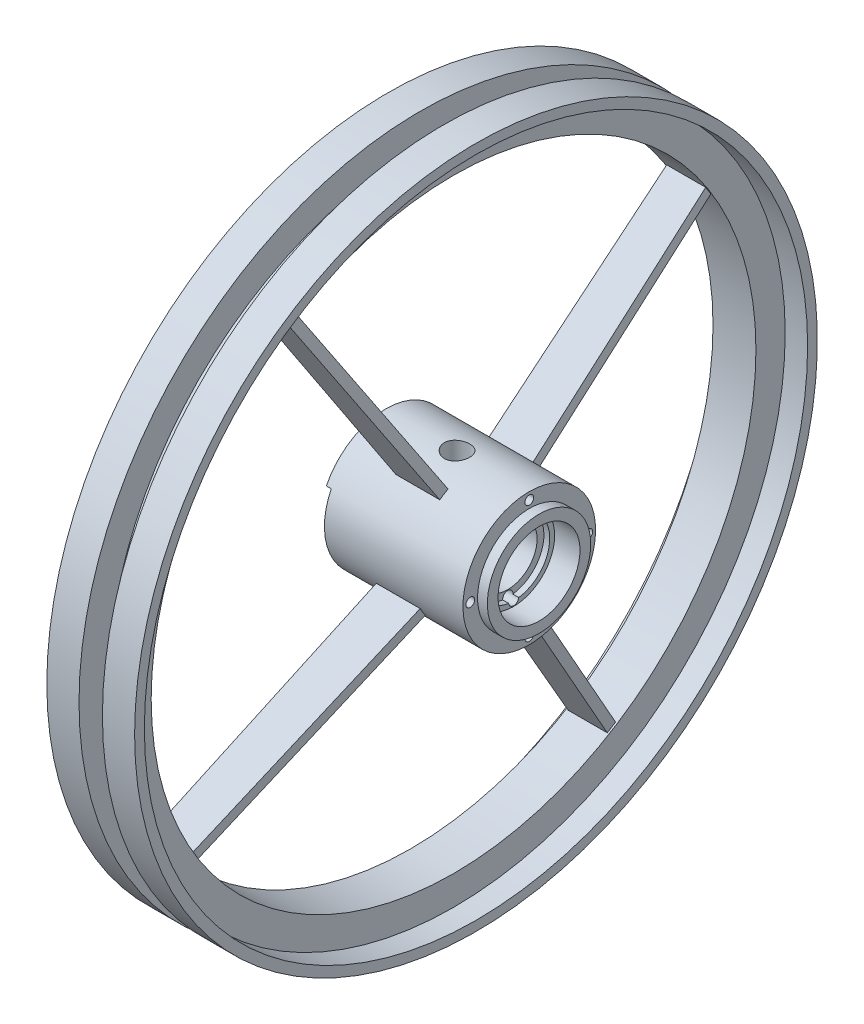
SolidWorks part; units mm, degrees
ref_plane "Front Plane" through (0, 0, 0) normal (0, 0, 1) x (1, 0, 0)
ref_plane "Top Plane" through (0, 0, 0) normal (0, 1, 0) x (1, 0, 0)
ref_plane "Right Plane" through (0, 0, 0) normal (1, 0, 0) x (0, 0, -1)
sketch "Sketch17" plane through (0, 0, 0) normal (0, 0, 1) x (1, 0, 0)
  line L0 (0, 0) -> (156.5215, 0) construction
sketch "Sketch1" plane through (0, 0, 0) normal (1, 0, 0) x (0, 0, -1)
  circle A0 centre (0, 0) radius 68
extrude "Boss-Extrude1" add sketch "Sketch1" along normal blind 157 contours A0
sketch "Sketch2" plane through (0, 0, 0) normal (-1, 0, 0) x (0, 0, 1)
  circle A0 centre (0, 0) radius 26
extrude "Cut-Extrude1" cut sketch "Sketch2" against normal up to next
sketch "Sketch3" plane through (0, 0, 0) normal (-1, 0, 0) x (0, 0, 1)
  line L1 (-68, 30) -> (68, 30)
  line L2 (-68, 30) -> (-68, -68)
  line L3 (-68, -68) -> (68, -68)
  line L4 (68, 30) -> (68, -68)
  circle A2 centre (0, 0) radius 68 construction
  circle A3 centre (0, 0) radius 26 construction
  dimension "D1" = 30
  dimension "D2" = 68
  dimension "D3" = 42
  dimension "D4" = 68
  dimension "D5" = 68
extrude "Cut-Extrude2" cut sketch "Sketch3" against normal blind 5 contours L2 L3 L4 L1
sketch "Sketch4" plane through (5, 0, 0) normal (-1, 0, 0) x (0, 0, 1)
  line L3 (-13.5, 29) -> (13.5, 29)
  arc A2 (13.5, 29) -> (-13.5, 29) centre (0, 0) cw
  dimension "D1" = 27
  dimension "D2" = 29
extrude "Cut-Extrude3" cut sketch "Sketch4" against normal blind 44
sketch "Sketch7" plane through (157, 0, 0) normal (1, 0, 0) x (0, 0, -1)
  circle A0 centre (0, 0) radius 42
extrude "Cut-Extrude4" cut sketch "Sketch7" against normal blind 26
sketch "Sketch8" plane through (131, 0, 0) normal (1, 0, 0) x (0, 0, -1)
  circle A0 centre (0, 0) radius 37
extrude "Cut-Extrude5" cut sketch "Sketch8" against normal blind 6 contours A0
sketch "Sketch9" plane through (125, 0, 0) normal (1, 0, 0) x (0, 0, -1)
  circle A0 centre (0, 0) radius 30
extrude "Cut-Extrude6" cut sketch "Sketch9" against normal blind 28 contours A0
ref_plane "Plane2" through (0, 0, 68) normal (0, 0, 1) x (1, 0, 0)
sketch "Sketch12" plane through (0, 0, 68) normal (0, 0, 1) x (1, 0, 0)
  line L0 (49, 37.9633) -> (49, -31.4216)
  line L1 (49, -31.4216) -> (59.8739, -42.2955)
  line L2 (59.8739, -42.2955) -> (85.8739, -42.2955)
  line L3 (85.8739, -42.2955) -> (97, -31.1695)
  line L4 (97, -31.1695) -> (97, 37.7112)
  line L5 (97, 37.7112) -> (85.8739, 48.8372)
  line L6 (85.8739, 48.8372) -> (59.8739, 48.8372)
  line L7 (59.8739, 48.8372) -> (49, 37.9633)
  line L8 (157, -68) -> (157, 68) construction
  line L9 (5, 30) -> (5, -68) construction
  point P12 (59.8739, 48.8372)
  dimension "D1" = 60
  dimension "D2" = 44
  dimension "D3" = 26
  dimension "D4" = 26
  dimension "D5" = 135
  dimension "D6" = 135
  dimension "D7" = 135
  dimension "D8" = 135
sketch "Sketch16" plane through (0, 0, 0) normal (-1, 0, 0) x (0, 0, 1)
  line L0 (35.9404, 57.726) -> (61.0246, 30) construction
  line L1 (35.9404, 57.726) -> (0, 68) construction
  arc A0 (61.0246, 30) -> (-61.0246, 30) centre (0, 0) ccw construction
  dimension "D1" = 37.38
  dimension "D2" = 37.3892
ref_plane "Plane5" through (0, 68, 0) normal (0, 1, 0) x (1, 0, 0)
ref_plane "Plane7" through (0, 0, 0) normal (0, 0, 1) x (1, 0, 0)
sketch "Sketch23" plane through (0, 68, 0) normal (0, 1, 0) x (1, 0, 0)
  line L0 (86, -40) -> (86, 40) construction
  point P9 (73, 0)
  dimension "D1" = 13
sketch "Sketch27" plane through (157, 0, 0) normal (1, 0, 0) x (0, 0, -1)
  circle A0 centre (0, 0) radius 68
  circle A1 centre (0, 0) radius 53
  dimension "D1" = 136
  dimension "D2" = 106
extrude "Cut-Extrude9" cut sketch "Sketch27" against normal blind 10
sketch "Sketch36" plane through (0, 0, 0) normal (0, 0, 1) x (1, 0, 0)
  line L0 (49, 29) -> (60, 40)
  line L1 (60, 40) -> (86, 40)
  line L2 (86, 40) -> (97, 29)
  line L8 (147, 68) -> (0, 68) construction
  line L17 (49, 29) -> (49, 0)
  line L18 (0, 0) -> (156.5215, 0) construction
  line L19 (49, 0) -> (97, 0)
  line L20 (97, 0) -> (97, 29)
  line L21 (157, -53) -> (157, 53) construction
  line L22 (5, 30) -> (5, -68) construction
  point P14 (85.7305, 38.7511)
  point P15 (59.8636, 40)
  point P16 (0, 0)
  dimension "D1" = 60
  dimension "D2" = 44
  dimension "D3" = 135
  dimension "D4" = 40
  dimension "D5" = 26
revolve "Cut-Revolve2" cut sketch "Sketch36" angle 360 about L0
hole_wizard "Tap Drill for M1.2x0.25 Tap1" positions "Sketch23" profile "Sketch26" hole size "M1.2x0.25" standard "ISO"
sketch "Sketch26" plane through (73, 68, 0) normal (1, 0, 0) x (0, 0, 1)
  line L0 (0, 0) -> (0, 68)
  line L1 (0, 68) -> (13, 68)
  line L2 (13, 68) -> (13, 0)
  line L5 (13, 0) -> (0, 0)
  line L10 (0, 68) -> (-13, 68) construction
  line L11 (0, -6.35) -> (0, 107.95) construction
  dimension "Hole Dia." = 26
  dimension "Hole Depth" = 68
  dimension "Drill Angle" = 180
sketch "Sketch29" plane through (147, 0, 0) normal (1, 0, 0) x (0, 0, -1)
  line L0 (0, 68) -> (0, 53) construction
  line L1 (53, 0) -> (68, 0) construction
  line L2 (0, -53) -> (0, -68) construction
  line L3 (-53, 0) -> (-68, 0) construction
  line L4 (-68, 74.8) -> (-68, -74.8) construction
  circle A0 centre (0, 0) radius 53 construction
  circle A1 centre (0, 0) radius 53 construction
  circle A2 centre (0, 0) radius 68 construction
  point P21 (0, 60.5)
  point P23 (60.5, 0)
  point P25 (0, -60.5)
  point P27 (-60.5, 0)
hole_wizard "M8 Clearance Hole1" positions "Sketch29" profile "Sketch30" hole size "M8" standard "ISO"
sketch "Sketch30" plane through (147, 0, 60.5) normal (0, 1, 0) x (0, 0, -1)
  line L0 (0, 0) -> (0, 37.7039)
  line L1 (0, 37.7039) -> (4.5, 35)
  line L2 (4.5, 35) -> (4.5, 0)
  line L5 (4.5, 0) -> (0, 0)
  line L10 (0, 37.7039) -> (-4.5, 35) construction
  line L11 (0, -6.35) -> (0, 107.95) construction
  dimension "Hole Dia." = 9
  dimension "Hole Depth" = 35
  dimension "Drill Angle" = 118
ref_plane "Plane4" through (0, 0, 0) normal (0, 0.5285, -0.8489) x (-1, 0, 0)
sketch "Sketch19" plane through (0, 0, 0) normal (0, 0.5285, -0.8489) x (-1, 0, 0)
  line L1 (-97, 30) -> (-97, -30) construction
  line L3 (-27.3689, 310) -> (-67.3689, 310)
  line L9 (0, 0) -> (-156.5215, 0) construction
  line L10 (-67.3689, 310) -> (-95.5, 66.5)
  line L11 (-95.5, 66.5) -> (-50.5, 66.5)
  line L12 (-50.5, 66.5) -> (-27.3689, 310)
  line L13 (0, 68) -> (-147, 68) construction
  point P8 (0, 0)
  dimension "D1" = 310
  dimension "D2" = 83.41
  dimension "D3" = 45
  dimension "D4" = 1.5
  dimension "D5" = 1.5
  dimension "D6" = 40
sketch "Sketch21" plane through (0, 0, 0) normal (0, 0.5285, -0.8489) x (-1, 0, 0)
  line L0 (-67.3689, 310) -> (-69.3689, 310)
  line L1 (-69.3689, 310) -> (-69.3689, 340)
  line L2 (-69.3689, 340) -> (-92.3689, 340)
  line L3 (-92.3689, 340) -> (-92.3689, 350)
  line L4 (-92.3689, 350) -> (-59.3689, 350)
  line L5 (-2.3689, 350) -> (-2.3689, 340)
  line L6 (-2.3689, 340) -> (-25.3689, 340)
  line L7 (-25.3689, 340) -> (-25.3689, 310)
  line L8 (-25.3689, 310) -> (-27.3689, 310)
  line L11 (-59.3689, 350) -> (-59.3689, 320)
  line L12 (-59.3689, 320) -> (-35.3689, 320)
  line L13 (-35.3689, 320) -> (-35.3689, 350)
  line L14 (-35.3689, 350) -> (-2.3689, 350)
  line L15 (-27.3689, 310) -> (-67.3689, 310) construction
  line L17 (-67.3689, 310) -> (-27.3689, 310)
  dimension "D2" = 10
  dimension "D3" = 10
  dimension "D7" = 10
  dimension "D8" = 90
  dimension "D11" = 40
  dimension "D12" = 40
  dimension "D10" = 2
  dimension "D5" = 2
  dimension "D6" = 10
  dimension "D9" = 10
  dimension "D4" = 23
  dimension "D13" = 24
revolve "Revolve1" add sketch "Sketch21" angle 360 about L0
extrude "Boss-Extrude4" add sketch "Sketch19" along normal mid plane 10
pattern_circular "CirPattern4" count 4 every 90 about axis through (0, 0, 0) along (1, 0, 0) of "Boss-Extrude4"
sketch "Esquisse4" plane through (131, 0, 0) normal (1, 0, 0) x (0, 0, -1)
  line L0 (0, 0) -> (0, -36) construction
  point P11 (0, -36)
  dimension "D1" = 36
  dimension "D2" = 0
hole_wizard "M10 Clearance Hole1" positions "Esquisse4" profile "Esquisse6" hole size "M10" standard "ANSI Metric"
sketch "Esquisse6" plane through (131, -36, 0) normal (0, 1, 0) x (0, 0, -1)
  line L0 (0, 0) -> (0, 15)
  line L1 (0, 15) -> (5.25, 15)
  line L2 (5.25, 15) -> (5.25, 0)
  line L5 (5.25, 0) -> (0, 0)
  line L10 (0, 15) -> (-5.25, 15) construction
  line L11 (0, -6.35) -> (0, 107.95) construction
  dimension "Hole Dia." = 10.5
  dimension "Hole Depth" = 15
  dimension "Drill Angle" = 180
equation "\"D1@Sketch3\"=26+8/2"
equation "\"D2@Sketch3\"=26+\"D3@Sketch3\""
equation "\"D4@Sketch3\"=\"D2@Sketch3\""
equation "\"D5@Sketch3\"=\"D2@Sketch3\""
equation "\"D12@Sketch21\"=\"D11@Sketch21\""
equation "\"D2@Sketch27\"=\"D1@Sketch27\"-15*2"
equation "\"D4@Sketch21\"=(\"D8@Sketch21\"-\"D6@Sketch21\"-\"D13@Sketch21\"-\"D9@Sketch21\")/2"
